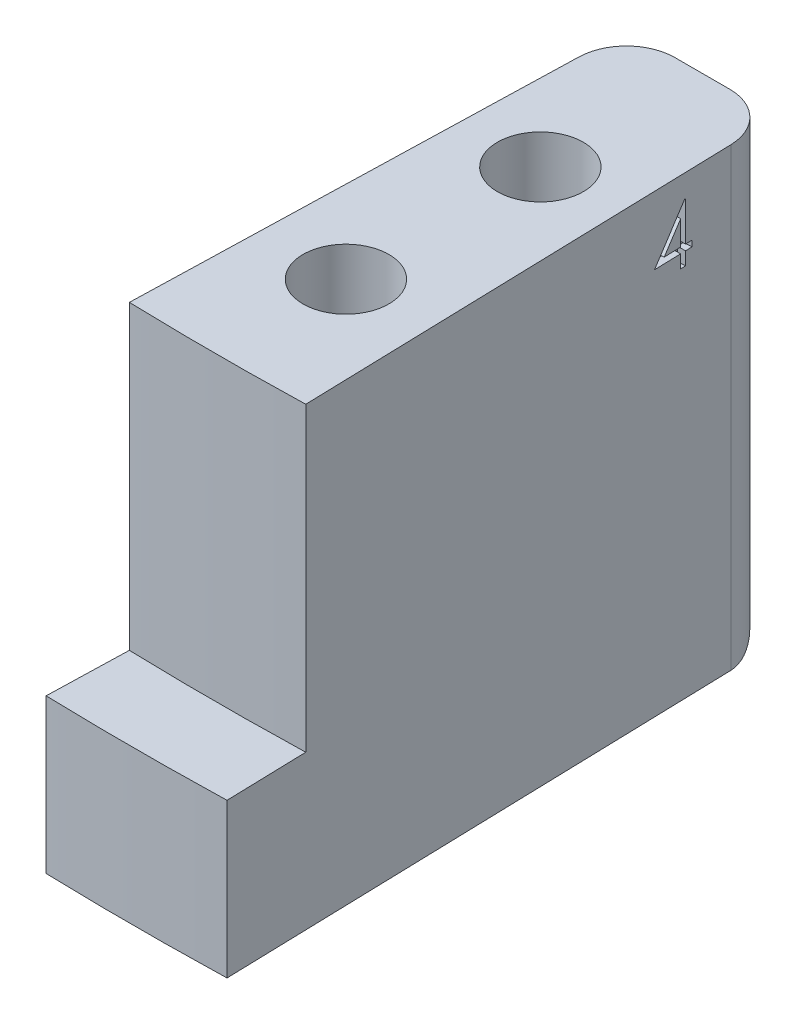
SolidWorks part; units mm, degrees
ref_plane "前视基准面" through (0, 0, 0) normal (0, 0, 1) x (1, 0, 0)
ref_plane "上视基准面" through (0, 0, 0) normal (0, 1, 0) x (1, 0, 0)
ref_plane "右视基准面" through (0, 0, 0) normal (1, 0, 0) x (0, 0, -1)
ref_axis "顶盖中心轴" through (0, -55, 0) along (0, 1, 0)
sketch "草图1" plane through (0, 0, 0) normal (0, 1, 0) x (1, 0, 0)
  line L0 (-4.7487, -170.0072) -> (-4.8586, -173.9402) construction
  line L1 (0, 0) -> (0, -125.794) construction
  line L3 (-4.6089, -165) -> (4.6089, -165)
  line L4 (-4.6089, -165) -> (-5.5843, -199.922)
  line L5 (4.6089, -165) -> (5.5843, -199.922)
  arc A0 (-5.4447, -194.924) -> (5.4447, -194.924) centre (0, 0) ccw
  arc A1 (-5.5843, -199.922) -> (5.5843, -199.922) centre (0, 0) ccw
  dimension "D1" = 1.6
  dimension "D2" = 195
  dimension "D4" = 200
  dimension "D3" = 165
extrude "主体" add sketch "草图1" along normal blind 28.1 contours L4 A0 L5 L3 region at (0, 0, 180.4033)
extrude "插销" add sketch "草图1<3>" along normal blind 9.5 contours L4 A1 L5 A0 region at (0, 0, 197.4849)
sketch "草图1<3>" plane through (0, 0, 0) normal (0, 1, 0) x (1, 0, 0) same geometry as "草图1"
ref_plane "对称面" through (0, 0, 0) normal (1, 0, 0) x (0, 0, -1)
fillet "圆角1" radius 3 3 edges at (-4.6089, 14.05, 165) (4.6089, 14.05, 165) (0, 0, 165)
hole_wizard "M5 间隙孔1" positions "草图4" profile "草图5" hole size "M5" standard "ISO" end condition up to next
sketch "草图4" plane through (0, 28.1, 0) normal (0, 1, 0) x (1, 0, 0)
  line L0 (0, -13.75) -> (0, 13.75) construction
  point P0 (0, -187)
  point P2 (0, -175)
  dimension "D1" = 175
  dimension "D2" = 187
sketch "草图5" plane through (0, 28.1, 187) normal (1, 0, 0) x (0, 0, 1)
  line L0 (0, 0) -> (0, 28.1)
  line L1 (0, 28.1) -> (2.65, 28.1)
  line L2 (2.65, 28.1) -> (2.65, 0)
  line L5 (2.65, 0) -> (0, 0)
  line L11 (0, -6.35) -> (0, 107.95) construction
  dimension "通孔孔直径" = 5.3
  dimension "通孔孔深度" = 28.1
sketch "草图6" plane through (0, 0, 0) normal (0, -1, 0) x (1, 0, 0)
  line L1 (0, 179.6188) -> (-4, 177.3094)
  line L2 (-4, 177.3094) -> (-4, 172.6906)
  line L3 (-4, 172.6906) -> (0, 170.3812)
  line L4 (0, 170.3812) -> (4, 172.6906)
  line L5 (4, 172.6906) -> (4, 177.3094)
  line L6 (4, 177.3094) -> (0, 179.6188)
  line L7 (0, 191.6188) -> (-4, 189.3094)
  line L8 (-4, 189.3094) -> (-4, 184.6906)
  line L9 (-4, 184.6906) -> (0, 182.3812)
  line L10 (0, 182.3812) -> (4, 184.6906)
  line L11 (4, 184.6906) -> (4, 189.3094)
  line L12 (4, 189.3094) -> (0, 191.6188)
  circle A0 centre (0, 175) radius 4 construction
  circle A1 centre (0, 187) radius 4 construction
  dimension "D1" = 8
  dimension "D2" = 8
extrude "切除-拉伸1" cut sketch "草图6" against normal blind 5
sketch "草图7" plane through (0, 0, 0) normal (0.9996, 0, -0.0279) x (-0.0279, 0, -0.9996)
  line L0 (-167.9817, 0.0012) -> (-167.9817, 28.1) construction
  line L2 (-167.9817, 28.1) -> (-195, 28.1) construction
  text T0 "4"
  dimension "D1" = 5
  dimension "D2" = 5
extrude "切除-拉伸2" cut sketch "草图7" against normal blind 0.5
